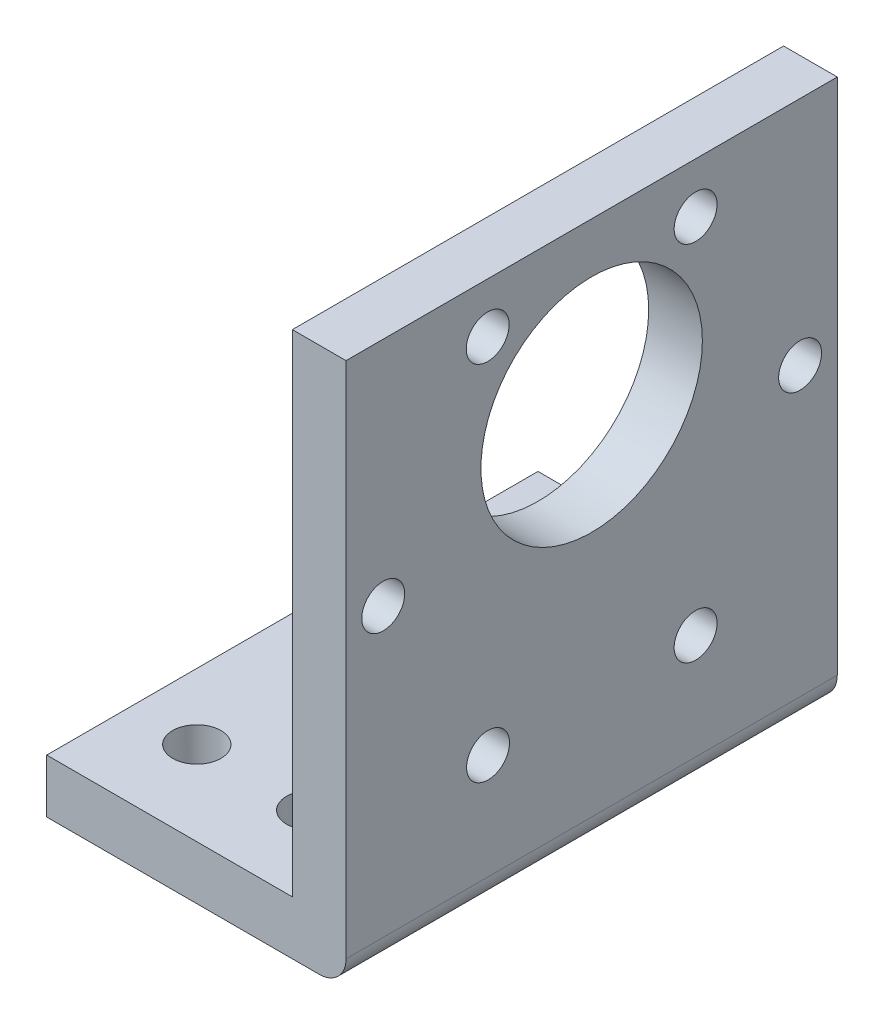
SolidWorks part; units mm, degrees
ref_plane "前视基准面" through (0, 0, 0) normal (0, 0, 1) x (1, 0, 0)
ref_plane "上视基准面" through (0, 0, 0) normal (0, 1, 0) x (1, 0, 0)
ref_plane "右视基准面" through (0, 0, 0) normal (1, 0, 0) x (0, 0, -1)
sketch "草图1" plane through (0, 0, 0) normal (0, 1, 0) x (1, 0, 0)
  line L1 (11.15, -18.3) -> (-11.15, -18.3)
  line L2 (11.15, -18.3) -> (11.15, 18.3)
  line L3 (11.15, 18.3) -> (-11.15, 18.3)
  line L4 (-11.15, -18.3) -> (-11.15, 18.3)
  line L5 (11.15, -18.3) -> (-11.15, 18.3) construction
  line L6 (11.15, 18.3) -> (-11.15, -18.3) construction
  point P0 (0, 0)
  dimension "D1" = 36.6
  dimension "D2" = 22.3
extrude "凸台-拉伸1" add sketch "草图1" along normal blind 40.6
ref_plane "基准面1" through (0, 40.6, 0) normal (0, 1, 0) x (1, 0, 0)
sketch "草图2" plane through (0, 40.6, 0) normal (0, 1, 0) x (1, 0, 0)
  line L0 (-11.15, -18.3) -> (11.15, -18.3) construction
  line L1 (-11.15, 18.3) -> (7.15, 18.3)
  line L2 (-11.15, 18.3) -> (-11.15, -18.3)
  line L3 (-11.15, -18.3) -> (7.15, -18.3)
  line L4 (7.15, 18.3) -> (7.15, -18.3)
  dimension "D1" = 18.3
extrude "切除-拉伸1" cut sketch "草图2" against normal blind 36.6
ref_plane "基准面2" through (11.15, 0, 0) normal (1, 0, 0) x (0, 0, -1)
sketch "草图3" plane through (11.15, 0, 0) normal (1, 0, 0) x (0, 0, -1)
  line L0 (2.2, 40.6) -> (-2.2, 40.6) construction
  line L1 (-18.3, 40.6) -> (18.3, 40.6)
  line L2 (-18.3, 40.6) -> (-18.3, 4)
  line L3 (-18.3, 4) -> (18.3, 4)
  line L4 (18.3, 40.6) -> (18.3, 4)
  line L5 (-18.3, 40.6) -> (-18.3, 0) construction
  line L6 (18.3, 40.6) -> (18.3, 0) construction
  line L7 (0, 40.6) -> (0, 36.8637) construction
  line L8 (0, 36.8637) -> (0, 28.6137) construction
  line L9 (7.7452, 36.8637) -> (-7.7452, 36.8637)
  line L10 (-7.7452, 36.8637) -> (-15.53, 23.3801) construction
  line L11 (7.7452, 36.8637) -> (15.53, 23.3801) construction
  line L12 (-15.53, 23.3801) -> (-7.719, 9.851) construction
  line L13 (-7.719, 9.851) -> (7.7452, 9.851) construction
  line L14 (7.7452, 9.851) -> (15.53, 23.3801) construction
  circle A0 centre (0, 28.6137) radius 8.25
  circle A1 centre (-7.7452, 36.8637) radius 1.6
  circle A2 centre (7.7452, 36.8637) radius 1.6
  circle A3 centre (-15.53, 23.3801) radius 1.6
  circle A4 centre (15.53, 23.3801) radius 1.6
  circle A5 centre (7.7452, 9.851) radius 1.6
  circle A6 centre (-7.719, 9.851) radius 1.6
  point P10 (0, 40.6)
  point P20 (0, 36.8637)
  dimension "D2" = 120
  dimension "D4" = 16.5
  dimension "D1" = 36.6
  dimension "D3" = 120
extrude "切除-拉伸5" cut sketch "草图3" against normal blind 36.6 contours A0 | A1 | A3 | A2 | A4 | A5 | A6 region at (11.15, 28.6137, 0) region at (11.15, 36.8637, 9.3) region at (11.15, 38.4184, -7.7452) region at (11.15, 23.3801, 15.53) region at (11.15, 23.3801, -15.53) region at (11.15, 9.851, -7.7452) region at (11.15, 9.851, 7.719)
ref_plane "基准面3" through (0, 0, 0) normal (0, -1, 0) x (-1, 0, 0)
sketch "草图4" plane through (0, 0, 0) normal (0, -1, 0) x (-1, 0, 0)
  line L0 (11.15, 0) -> (-7.15, 0) construction
  line L1 (11.15, 18.3) -> (-7.15, 18.3)
  line L2 (11.15, 18.3) -> (11.15, -18.3)
  line L3 (11.15, -18.3) -> (-7.15, -18.3)
  line L4 (-7.15, 18.3) -> (-7.15, -18.3)
  line L5 (2, -18.3) -> (2, 18.3)
  circle A5 centre (-2.2427, 12.0271) radius 1.8
  circle A6 centre (6.2427, 12.0271) radius 1.8
  circle A7 centre (6.2427, -12.0271) radius 1.8
  circle A8 centre (-2.2427, -12.0271) radius 1.8
  point P6 (11.15, 0)
  point P12 (2, 0)
  dimension "D1" = 24.0542
  dimension "D2" = 8.4853
extrude "切除-拉伸7" cut sketch "草图4" against normal blind 36.6 contours A5 | A6 | A7 | A8 region at (2.2427, 0, -12.0271) region at (-6.2427, 0, -12.0271) region at (-6.2427, 0, 12.0271)
ref_plane "基准面4" through (-11.15, 0, 18.3) normal (1, 0, 0) x (0, 0, -1)
fillet "圆角1" radius 2 1 edges at (11.15, 0, 0)
